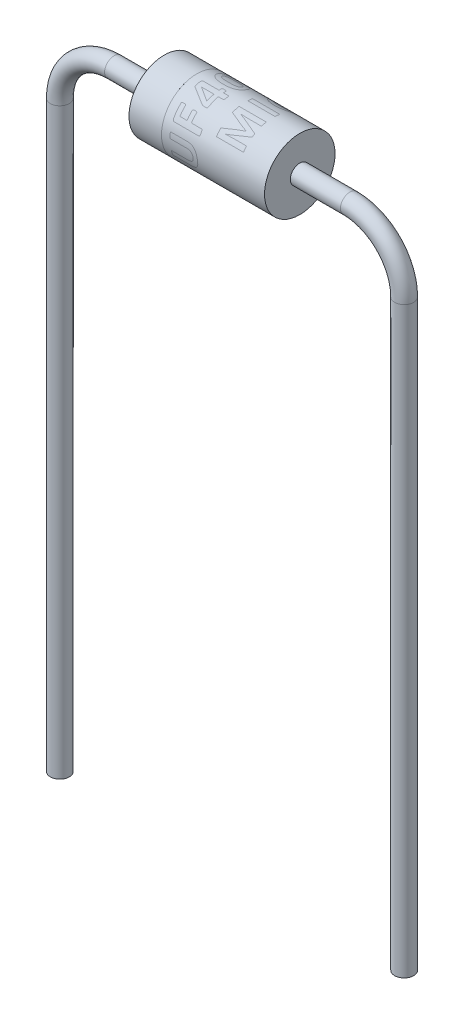
SolidWorks part; units mm, degrees
other "Diode"
other "Cathode Silver Band"
other "Wire"
ref_plane "Front Plane" through (0, 0, 0) normal (0, 0, 1) x (1, 0, 0)
ref_plane "Top Plane" through (0, 0, 0) normal (0, 1, 0) x (1, 0, 0)
ref_plane "Right Plane" through (0, 0, 0) normal (1, 0, 0) x (0, 0, -1)
sketch "Sketch1" plane through (0, 0, 0) normal (1, 0, 0) x (0, 0, -1)
  circle A0 centre (0, 0) radius 1.3
  circle A1 centre (0, 0) radius 0.35
  dimension "D1" = 2.6
  dimension "D2" = 0.7
extrude "Boss-Extrude1" add sketch "Sketch1" along normal mid plane 5
sketch "Sketch2" plane through (-2.5, 0, 0) normal (-1, 0, 0) x (0, 0, 1)
  circle A1 centre (0, 0) radius 1.3 construction
  circle A2 centre (0, 0) radius 1.29
  circle A3 centre (0, 0) radius 1.29
  circle A4 centre (0, 0) radius 1.3
  dimension "D1" = 0.01
extrude "Cut-Extrude1" cut sketch "Sketch2" against normal blind 1.2
sketch "Sketch3" plane through (-1.3, 0, 0) normal (-1, 0, 0) x (0, 0, 1)
  circle A0 centre (0, 0) radius 1.29 construction
  circle A1 centre (0, 0) radius 1.29
  circle A2 centre (0, 0) radius 1.3 construction
  circle A3 centre (0, 0) radius 1.3
extrude "Boss-Extrude2" add sketch "Sketch3" along normal up to surface (1.2 mm away) separate body up to face at (-2.5, 0, -0.35)
ref_plane "Plane1" through (0, 5, 0) normal (0, 1, 0) x (1, 0, 0)
sketch "Sketch4" plane through (0, 5, 0) normal (0, 1, 0) x (1, 0, 0)
  line L0 (0, 7.5) -> (0, -7.5) construction
  line L1 (0, 0) -> (-2.5, 0) construction
  line L2 (-2.5, 1.3) -> (-2.5, -1.3) construction
  line L4 (0, 0) -> (1.5, 0) construction
  line L5 (1.5, 7.5) -> (1.5, -7.5) construction
  text T0 "UF4007" font "Calibri" height 1
  text T1 "MIC" font "Corbel" height 1
  dimension "D1" = 2.5
  dimension "D2" = 15
  dimension "D3" = 1.5
wrap "Wrap1" sketch "Sketch4" wrap type scribe source sketch "Sketch4" face at (2.5, 0, -1.3)
sketch "Sketch5" plane through (0, 0, 0) normal (0, 0, 1) x (1, 0, 0)
  line L0 (0, 0) -> (-4.35, 0)
  line L1 (-6.35, -2) -> (-6.35, -23.5084)
  line L2 (0, 0) -> (4.35, 0)
  line L3 (6.35, -2) -> (6.35, -23.5084)
  arc A0 (-4.35, 0) -> (-6.35, -2) centre (-4.35, -2) ccw
  arc A1 (4.35, 0) -> (6.35, -2) centre (4.35, -2) cw
  dimension "D2" = 2
  dimension "D3" = 58
  dimension "D1" = 12.7
sketch "Sketch6" plane through (0, 0, 0) normal (1, 0, 0) x (0, 0, -1)
  circle A0 centre (0, 0) radius 0.35
  dimension "D1" = 0.7
sweep "Sweep1" add profiles "Sketch6" path "Sketch5"
